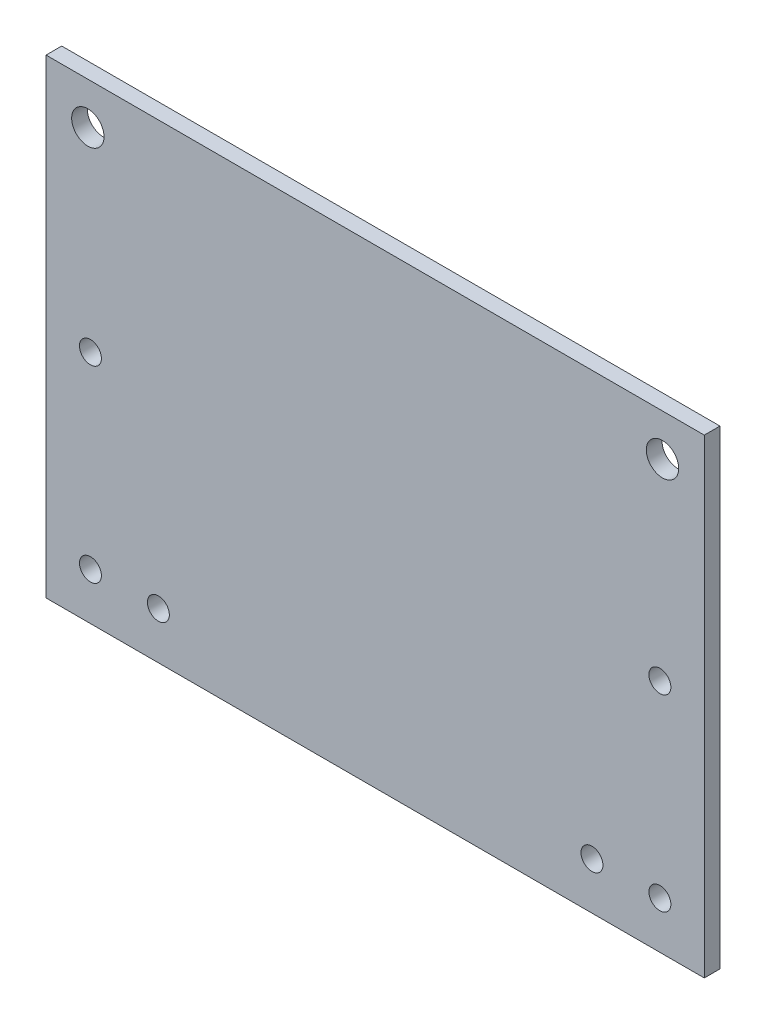
SolidWorks part; units mm, degrees
material "Stop 1060"
ref_plane "Płaszczyzna przednia" through (0, 0, 0) normal (0, 0, 1) x (1, 0, 0)
ref_plane "Płaszczyzna górna" through (0, 0, 0) normal (0, 1, 0) x (1, 0, 0)
ref_plane "Płaszczyzna prawa" through (0, 0, 0) normal (1, 0, 0) x (0, 0, -1)
sketch "Szkic1" plane through (0, 0, 0) normal (0, 0, 1) x (1, 0, 0)
  line L1 (0, 0) -> (126, 0)
  line L2 (0, 0) -> (0, 90)
  line L3 (0, 90) -> (126, 90)
  line L4 (126, 0) -> (126, 90)
  dimension "D1" = 126
  dimension "D2" = 90
extrude "Dodanie-wyciągnięcie1" add sketch "Szkic1" along normal blind 3
sketch "Szkic2" plane through (0, 0, 3) normal (0, 0, 1) x (1, 0, 0)
  line L1 (0, 90) -> (0, 0) construction
  line L3 (0, 0) -> (126, 0) construction
  circle A0 centre (21.5, 9) radius 2.1
  circle A1 centre (104.5, 9) radius 2.1
  circle A2 centre (8.5, 9) radius 2.1
  circle A3 centre (117.5, 9) radius 2.1
  dimension "D3" = 4.2
  dimension "D4" = 8.5
  dimension "D5" = 21.5
  dimension "D6" = 9
  dimension "D1" = 83
  dimension "D2" = 109
extrude "Wytnij-wyciągnięcie1" cut sketch "Szkic2" against normal blind 3
sketch "Szkic3" plane through (0, 0, 3) normal (0, 0, 1) x (1, 0, 0)
  line L0 (0, 90) -> (0, 0) construction
  line L1 (126, 90) -> (0, 90) construction
  line L2 (126, 0) -> (126, 90) construction
  circle A0 centre (8, 82) radius 3.1
  circle A1 centre (118, 82) radius 3.1
  dimension "D1" = 8
  dimension "D2" = 8
  dimension "D3" = 6.2
  dimension "D4" = 8
extrude "Wytnij-wyciągnięcie2" cut sketch "Szkic3" against normal blind 10
sketch "Szkic4" plane through (0, 0, 3) normal (0, 0, 1) x (1, 0, 0)
  line L0 (63, 0) -> (63, 96.9345) construction
  line L1 (0, 0) -> (126, 0) construction
  circle A0 centre (8.5, 45) radius 2.1
  circle A1 centre (8.5, 9) radius 2.1 construction
  circle A2 centre (8.5, 9) radius 2.1
  circle A3 centre (117.5, 45) radius 2.1
  point P9 (0, 0)
  dimension "D1" = 4.2
  dimension "D2" = 36
extrude "Wytnij-wyciągnięcie3" cut sketch "Szkic4" against normal blind 10 contours A0 | A3 region at (8.5, 45, 3) region at (117.5, 45, 3)
